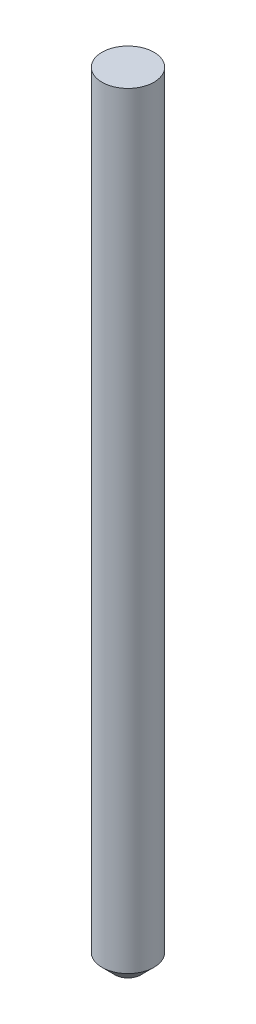
SolidWorks part; units mm, degrees
ref_plane "Front Plane" through (0, 0, 0) normal (0, 0, 1) x (1, 0, 0)
ref_plane "Top Plane" through (0, 0, 0) normal (0, 1, 0) x (1, 0, 0)
ref_plane "Right Plane" through (0, 0, 0) normal (1, 0, 0) x (0, 0, -1)
sketch "Sketch1" plane through (0, 0, 0) normal (0, 1, 0) x (1, 0, 0)
  circle A0 centre (0, 0) radius 4
  dimension "D1" = 8
extrude "Boss-Extrude1" add sketch "Sketch1" along normal blind 120
chamfer "Chamfer1" distance 2 angle 45 1 edges at (0, 0, 4)
sketch "Sketch3" plane through (0, 0, 0) normal (1, 0, 0) x (0, 0, -1)
  circle A0 centre (0, 0) radius 1.25
  dimension "D1" = 2.5
